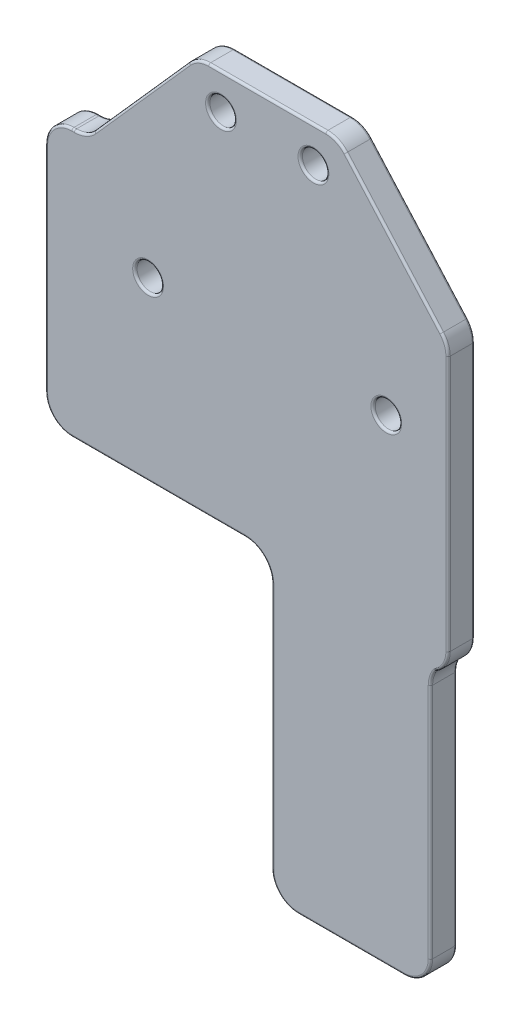
SolidWorks part; units mm, degrees
ref_plane "Front Plane" through (0, 0, 0) normal (0, 0, 1) x (1, 0, 0)
ref_plane "Top Plane" through (0, 0, 0) normal (0, 1, 0) x (1, 0, 0)
ref_plane "Right Plane" through (0, 0, 0) normal (1, 0, 0) x (0, 0, -1)
sketch "Sketch1" plane through (0, 0, 0) normal (0, 0, 1) x (1, 0, 0)
  line L0 (0, 0) -> (0, 62) construction
  line L4 (-20.5, 47.8997) -> (-7.9898, 62)
  line L5 (-7.9898, 62) -> (7.9898, 62)
  line L6 (20.5, 47.8997) -> (7.9898, 62)
  line L9 (13.5, 37.5997) -> (-13.5, 37.5997) construction
  line L11 (8.7303, 36.0997) -> (-8.7303, 36.0997) construction
  line L12 (8.7303, 36.0997) -> (8.7303, 39.0997) construction
  line L13 (8.7303, 39.0997) -> (-8.7303, 39.0997) construction
  line L14 (-8.7303, 36.0997) -> (-8.7303, 39.0997) construction
  line L15 (8.7303, 36.0997) -> (-8.7303, 39.0997) construction
  line L16 (8.7303, 39.0997) -> (-8.7303, 36.0997) construction
  line L19 (-20.5, 47.8997) -> (-25.1366, 47.8997)
  line L20 (-25.1366, 47.8997) -> (-25.1366, 17.5997)
  line L21 (-25.1366, 17.5997) -> (-20.5, 17.5997)
  line L22 (-20.5, 17.5997) -> (0.5, 17.5997)
  line L23 (0.5, 17.5997) -> (0.5, -16.4003)
  line L24 (20.5, 47.8997) -> (20.5, 15.2195)
  line L26 (20.5, 15.2195) -> (19.0702, 15.2195)
  line L27 (19.0702, 15.2195) -> (18.5, 14.7136)
  line L28 (18.5, 14.7136) -> (18.5, -16.4003)
  line L29 (18.5, -16.4003) -> (0.5, -16.4003)
  circle A0 centre (-5.2398, 58) radius 1.5
  circle A1 centre (-13.5, 37.5997) radius 1.5
  circle A4 centre (13.5, 37.5997) radius 1.5
  circle A5 centre (5.2398, 58) radius 1.5
  circle A7 centre (13.5, 37.5997) radius 5 construction
  circle A8 centre (-13.5, 37.5997) radius 5 construction
  point P11 (0, 0)
  point P12 (0, 0)
  point P17 (0, 0)
  point P18 (0, 0)
  point P19 (0, 0)
  point P30 (0, 0)
  point P34 (0, 0)
  point P39 (19.2414, 15.2195)
  point P40 (20.5, 28.9633)
  point P41 (0, 0)
  point P42 (20.5, 8.8694)
  point P43 (0, 0)
  point P44 (0, 0)
  point P45 (20.0702, 15.2195)
  dimension "D2" = 3
  dimension "D14" = 21
  dimension "D19" = 32.6802
  dimension "D1" = 62
  dimension "D3" = 10.4796
  dimension "D4" = 34
  dimension "D5" = 27
  dimension "D6" = 41
  dimension "D7" = 30.3
  dimension "D8" = 45.6366
  dimension "D9" = 10.3
  dimension "D10" = 2.75
  dimension "D11" = 4
  dimension "D12" = 18.85
  dimension "D13" = 18
  dimension "D15" = 4.6366
  dimension "D20" = 3
  dimension "D18" = 0.5059
  dimension "D16" = 3.5
  dimension "D17" = 3.5
extrude "Boss-Extrude1" add sketch "Sketch1" along normal blind 3
fillet "Fillet1" radius 3 11 edges at (-7.9898, 62, 1.5) (7.9898, 62, 1.5) (18.5, -16.4003, 1.5) (0.5, -16.4003, 1.5) (0.5, 17.5997, 1.5) (-25.1366, 17.5997, 1.5) (-25.1366, 47.8997, 1.5) (-20.5, 47.8997, 1.5) (20.5, 47.8997, 1.5) (18.5, 14.7136, 1.5) (20.5, 15.2195, 1.5)
fillet "Fillet2" radius 0.25 50 edges at (-12, 37.5997, 3) (-3.7398, 58, 3) (-14.2449, 54.9499, 3) (-7.8712, 61.7361, 3) (0, 62, 3) (7.8712, 61.7361, 3) (14.3146, 54.8714, 3) (12, 37.5997, 3) (3.7398, 58, 3) (12, 37.5997, 0) (-3.7398, 58, 0) (14.3146, 54.8714, 0) (7.8712, 61.7361, 0) (0, 62, 0) (-7.8712, 61.7361, 0) (-14.2449, 54.9499, 0) (-12, 37.5997, 0) (3.7398, 58, 0) (20.5, 32.2683, 3) (18.5, 0.0298, 3) (9.5, -16.4003, 3) (0.5, 0.5997, 3) (-12.3183, 17.5997, 3) (-25.1366, 32.7497, 3) (-21.9927, 47.8997, 3) (-21.9927, 47.8997, 0) (-25.1366, 32.7497, 0) (-12.3183, 17.5997, 0) (0.5, 0.5997, 0) (9.5, -16.4003, 0) (18.5, 0.0298, 0) (20.5, 32.2683, 0) (1.3787, -15.5216, 3) (-0.3787, 16.721, 3) (-24.2579, 18.4784, 3) (-24.2579, 47.021, 3) (-20.6186, 48.1636, 3) (17.6213, -15.5216, 3) (-20.6186, 48.1636, 0) (-24.2579, 47.021, 0) (-24.2579, 18.4784, 0) (-0.3787, 16.721, 0) (1.3787, -15.5216, 0) (17.6213, -15.5216, 0) (20.3047, 47.8256, 3) (20.3047, 47.8256, 0) (18.6461, 14.3848, 3) (18.6461, 14.3848, 0) (20.1183, 16.3113, 3) (20.1183, 16.3113, 0)
